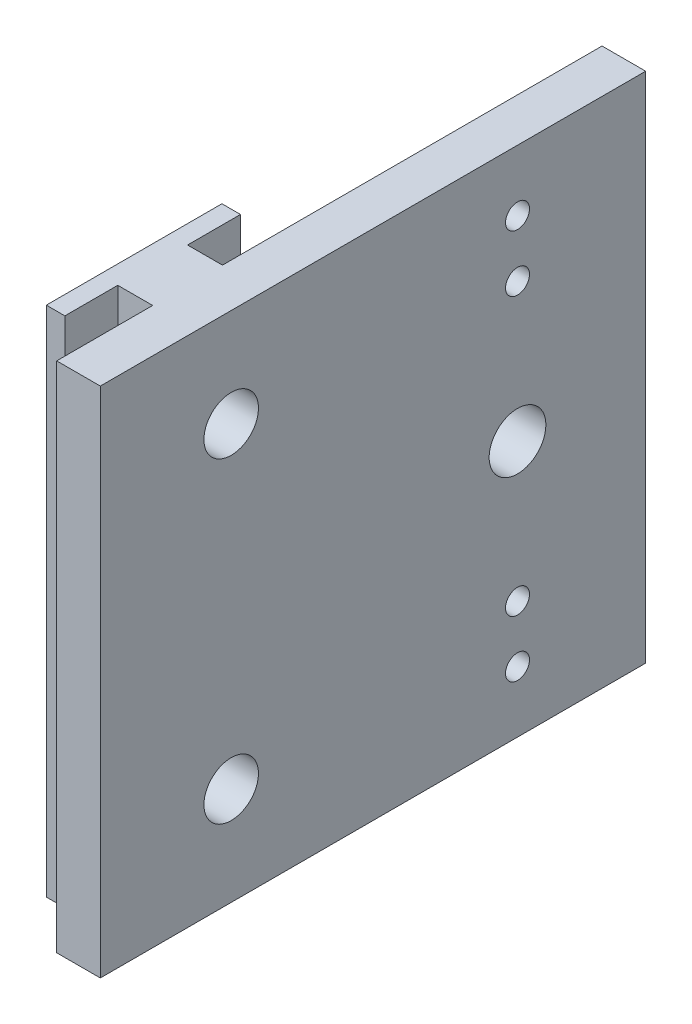
SolidWorks part; units mm, degrees
ref_plane "Front Plane" through (0, 0, 0) normal (0, 0, 1) x (1, 0, 0)
ref_plane "Top Plane" through (0, 0, 0) normal (0, 1, 0) x (1, 0, 0)
ref_plane "Right Plane" through (0, 0, 0) normal (1, 0, 0) x (0, 0, -1)
sketch "Sketch1" plane through (0, 0, 0) normal (0, 1, 0) x (1, 0, 0)
  line L0 (0, 0) -> (0, 20.447)
  line L1 (0, 20.447) -> (2.159, 20.447)
  line L2 (2.159, 20.447) -> (2.159, 14.2875)
  line L3 (2.159, 14.2875) -> (6.223, 14.2875)
  line L4 (6.223, 14.2875) -> (6.223, 58.4835)
  line L5 (6.223, 58.4835) -> (11.303, 58.4835)
  line L6 (11.303, 58.4835) -> (11.303, -5.0165)
  line L7 (11.303, -5.0165) -> (6.223, -5.0165)
  line L8 (6.223, -5.0165) -> (6.223, 6.1595)
  line L9 (6.223, 6.1595) -> (2.159, 6.1595)
  line L10 (2.159, 6.1595) -> (2.159, 0)
  line L11 (2.159, 0) -> (0, 0)
  line L12 (0, 10.2235) -> (11.303, 10.2235) construction
  line L13 (4.191, 14.2875) -> (4.191, 6.1595) construction
  point P17 (4.191, 14.2875)
  point P18 (4.191, 6.1595)
  point P19 (4.191, 10.2235)
  dimension "D1" = 20.447
  dimension "D2" = 2.159
  dimension "D3" = 4.064
  dimension "D4" = 8.128
  dimension "D5" = 5.08
  dimension "D6" = 63.5
  dimension "D7" = 48.26
extrude "Boss-Extrude1" add sketch "Sketch1" along normal blind 59.69 contours L6 L7 L8 L9 L10 L11 L0 L1 L2 L3 L4 L5
ref_axis "Axis1" through (1.0795, 0, -20.447) along (0, 1, 0)
sketch "Sketch2" plane through (11.303, 0, 0) normal (1, 0, 0) x (0, 0, -1)
  line L1 (43.561, 59.69) -> (43.561, 0) construction
  line L2 (58.4835, 59.69) -> (-5.0165, 59.69) construction
  line L3 (58.4835, 0) -> (-5.0165, 0) construction
  line L4 (20.447, 0) -> (20.447, 59.69) construction
  circle A0 centre (43.561, 29.845) radius 3.302
  circle A1 centre (43.561, 13.716) radius 1.397
  circle A2 centre (43.561, 7.112) radius 1.397
  circle A3 centre (43.561, 45.974) radius 1.397
  circle A4 centre (43.561, 52.578) radius 1.397
  dimension "D1" = 6.604
  dimension "D3" = 2.794
  dimension "D4" = 7.112
  dimension "D2" = 23.114
  dimension "D5" = 13.716
  dimension "D6" = 7.112
  dimension "D7" = 13.716
extrude "Cut-Extrude1" cut sketch "Sketch2" against normal through all
ref_axis "Axis2" through (0, 59.69, -10.2235) along (0, -1, 0)
sketch "Sketch3" plane through (0, 0, 0) normal (-1, 0, 0) x (0, 0, 1)
  line L0 (-10.2235, 59.69) -> (-10.2235, 0) construction
  line L1 (0, 59.69) -> (-20.447, 59.69) construction
  line L2 (0, 0) -> (-20.447, 0) construction
  circle A0 centre (-10.2235, 48.26) radius 3.175
  circle A1 centre (-10.2235, 11.43) radius 3.175
  dimension "D1" = 6.35
  dimension "D2" = 6.35
  dimension "D3" = 11.43
  dimension "D4" = 11.43
extrude "Cut-Extrude2" cut sketch "Sketch3" against normal through all
sketch "Sketch4" plane through (0, 0, 0) normal (-1, 0, 0) x (0, 0, 1)
  line L0 (-14.7955, 8.7904) -> (-14.7955, 14.0696)
  line L1 (-14.7955, 14.0696) -> (-10.2235, 16.7093)
  line L2 (-10.2235, 16.7093) -> (-5.6515, 14.0696)
  line L3 (-5.6515, 14.0696) -> (-5.6515, 8.7904)
  line L4 (-5.6515, 8.7904) -> (-10.2235, 6.1507)
  line L5 (-10.2235, 6.1507) -> (-14.7955, 8.7904)
  line L6 (-14.7955, 45.6204) -> (-14.7955, 50.8996)
  line L7 (-14.7955, 50.8996) -> (-10.2235, 53.5393)
  line L8 (-10.2235, 53.5393) -> (-5.6515, 50.8996)
  line L9 (-5.6515, 50.8996) -> (-5.6515, 45.6204)
  line L10 (-5.6515, 45.6204) -> (-10.2235, 42.9807)
  line L11 (-10.2235, 42.9807) -> (-14.7955, 45.6204)
  circle A0 centre (-10.2235, 11.43) radius 4.572
  circle A1 centre (-10.2235, 48.26) radius 4.572
  point P5 (0, 0)
  point P18 (-10.2235, 48.26)
  dimension "D1" = 9.144
  dimension "D2" = 9.144
extrude "Cut-Extrude3" cut sketch "Sketch4" against normal blind 2.0638 contours L0 L1 L2 L3 L4 L5 | L6 L7 L8 L9 L10 L11
